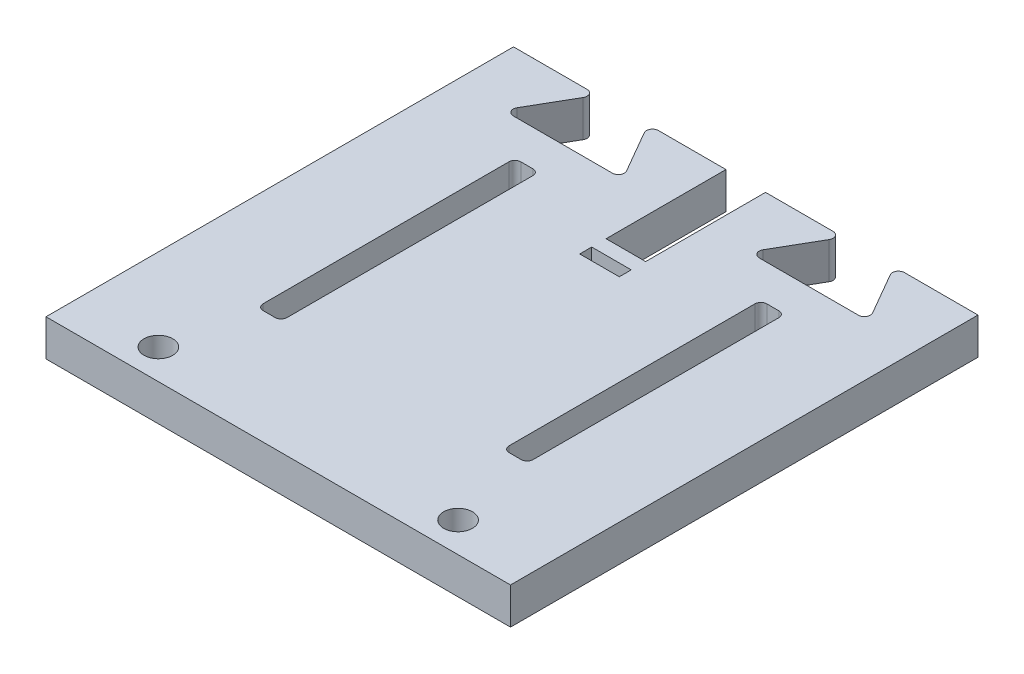
SolidWorks part; units mm, degrees
ref_plane "Front Plane" through (0, 0, 0) normal (0, 0, 1) x (1, 0, 0)
ref_plane "Top Plane" through (0, 0, 0) normal (0, 1, 0) x (1, 0, 0)
ref_plane "Right Plane" through (0, 0, 0) normal (1, 0, 0) x (0, 0, -1)
sketch "Sketch1" plane through (0, 0, 0) normal (0, 1, 0) x (1, 0, 0)
  line L0 (-19.375, 0) -> (-19.375, 39)
  line L1 (-19.375, 39) -> (-12.375, 39)
  line L2 (-12.375, 39) -> (-15.2618, 34)
  line L3 (-15.2618, 34) -> (-5.2618, 34)
  line L4 (-5.2618, 34) -> (-8.1485, 39)
  line L5 (-8.1485, 39) -> (8.1485, 39)
  line L6 (8.1485, 39) -> (5.2618, 34)
  line L7 (5.2618, 34) -> (15.2618, 34)
  line L8 (15.2618, 34) -> (12.375, 39)
  line L9 (12.375, 39) -> (19.375, 39)
  line L10 (19.375, 39) -> (19.375, 0)
  line L11 (19.375, 0) -> (-19.375, 0)
  point P3 (0, 0)
  dimension "D1" = 39
  dimension "D2" = 38.75
  dimension "D3" = 7
  dimension "D4" = 10
  dimension "D5" = 10
  dimension "D6" = 7
  dimension "D7" = 5
  dimension "D11" = 60
  dimension "D12" = 60
  dimension "D13" = 60
extrude "Boss-Extrude1" add sketch "Sketch1" along normal blind 3.05
fillet "Fillet3" radius 0.5 8 edges at (15.2618, 1.525, -34) (12.375, 1.525, -39) (5.2618, 1.525, -34) (8.1485, 1.525, -39) (-8.1485, 1.525, -39) (-5.2618, 1.525, -34) (-15.2618, 1.525, -34) (-12.375, 1.525, -39)
sketch "Sketch2" plane through (0, 3.05, 0) normal (0, 1, 0) x (1, 0, 0)
  line L0 (0, 0) -> (0, 32.5) construction
  line L3 (1.65, 29) -> (-1.65, 29)
  line L4 (1.65, 29) -> (1.65, 76)
  line L5 (1.65, 76) -> (-1.65, 76)
  line L6 (-1.65, 29) -> (-1.65, 76)
  line L7 (-1.65, 27.8) -> (1.65, 27.8)
  line L8 (-1.65, 27.8) -> (-1.65, 26.8)
  line L9 (-1.65, 26.8) -> (1.65, 26.8)
  line L10 (1.65, 27.8) -> (1.65, 26.8)
  line L11 (-19.375, 0) -> (19.375, 0) construction
  line L12 (-19.375, 0) -> (-19.375, 82.5) construction
  line L13 (-19.375, 82.5) -> (19.375, 82.5) construction
  line L14 (19.375, 0) -> (19.375, 82.5) construction
  point P8 (0, 29)
  point P13 (0, 27.8)
  dimension "D1" = 3.3
  dimension "D2" = 47
  dimension "D3" = 1
  dimension "D4" = 1.2
  dimension "D5" = 82.5
  dimension "D6" = 6.5
extrude "Cut-Extrude1" cut sketch "Sketch2" against normal through all
sketch "Sketch6" plane through (0, 3.05, 0) normal (0, 1, 0) x (1, 0, 0)
  line L0 (0, 0) -> (0, 18.0616) construction
  line L1 (-6.1278, 34) -> (-14.3957, 34) construction
  line L2 (-11.2618, 31) -> (-9.2618, 31)
  line L3 (-11.2618, 31) -> (-11.2618, 9.5)
  line L4 (-11.2618, 9.5) -> (-9.2618, 9.5)
  line L5 (-9.2618, 31) -> (-9.2618, 9.5)
  line L7 (11.2618, 9.5) -> (9.2618, 9.5)
  line L8 (9.2618, 31) -> (9.2618, 9.5)
  line L9 (11.2618, 31) -> (9.2618, 31)
  line L10 (11.2618, 31) -> (11.2618, 9.5)
  line L11 (-19.375, 0) -> (19.375, 0) construction
  point P9 (-10.2618, 34)
  point P10 (-10.2618, 31)
  dimension "D1" = 2
  dimension "D2" = 3
  dimension "D3" = 9.5
extrude "Cut-Extrude2" cut sketch "Sketch6" against normal through all
fillet "Fillet4" radius 0.5 8 edges at (9.2618, 1.525, -9.5) (11.2618, 1.525, -9.5) (11.2618, 1.525, -31) (9.2618, 1.525, -31) (-11.2618, 1.525, -9.5) (-9.2618, 1.525, -9.5) (-9.2618, 1.525, -31) (-11.2618, 1.525, -31)
sketch "Head Mounting Hole Locations" plane through (0, 3.05, 0) normal (0, 1, 0) x (1, 0, 0)
  line L0 (0, 0) -> (0, 16.3288) construction
  line L1 (-19.375, 0) -> (19.375, 0) construction
  circle A0 centre (-12.5, 2.5) radius 1.5
  circle A1 centre (12.5, 2.5) radius 1.5
  dimension "D1" = 3
  dimension "D2" = 12.5
  dimension "D3" = 2.5
hole_wizard "M3 Clearance Head Mounting Holes" positions "Sketch4" profile "Sketch5" hole size "M2" standard "ANSI Metric" end condition through all
sketch "Sketch4" plane through (0, 3.05, 0) normal (0, 1, 0) x (1, 0, 0)
  point P0 (-12.5, 2.5)
  point P3 (12.5, 2.5)
sketch "Sketch5" plane through (-12.5, 3.05, -2.5) normal (1, 0, 0) x (0, 0, 1)
  line L0 (0, 0) -> (0, 3.05)
  line L1 (0, 3.05) -> (1.2, 3.05)
  line L2 (1.2, 3.05) -> (1.2, 0)
  line L5 (1.2, 0) -> (0, 0)
  line L11 (0, -6.35) -> (0, 107.95) construction
  dimension "Thru Hole Dia." = 2.4
  dimension "Thru Hole Depth" = 3.05
sketch "Sketch7" plane through (0, 3.05, 0) normal (0, 1, 0) x (1, 0, 0)
  line L0 (-19.375, 39) -> (-18.875, 39)
  line L1 (-13.241, 39) -> (-19.375, 39) construction
  line L2 (-18.875, 39) -> (-18.875, 0)
  line L3 (-19.375, 0) -> (19.375, 0) construction
  line L4 (-18.875, 0) -> (-19.375, 0)
  line L5 (-19.375, 0) -> (-19.375, 39)
  line L6 (19.375, 39) -> (18.875, 39)
  line L7 (19.375, 39) -> (13.241, 39) construction
  line L8 (18.875, 39) -> (18.875, 0)
  line L9 (18.875, 0) -> (19.375, 0)
  line L10 (19.375, 0) -> (19.375, 39)
  dimension "D1" = 0.5
  dimension "D2" = 0.5
extrude "Cut-Extrude3" [suppressed] cut sketch "Sketch7" against normal through all
